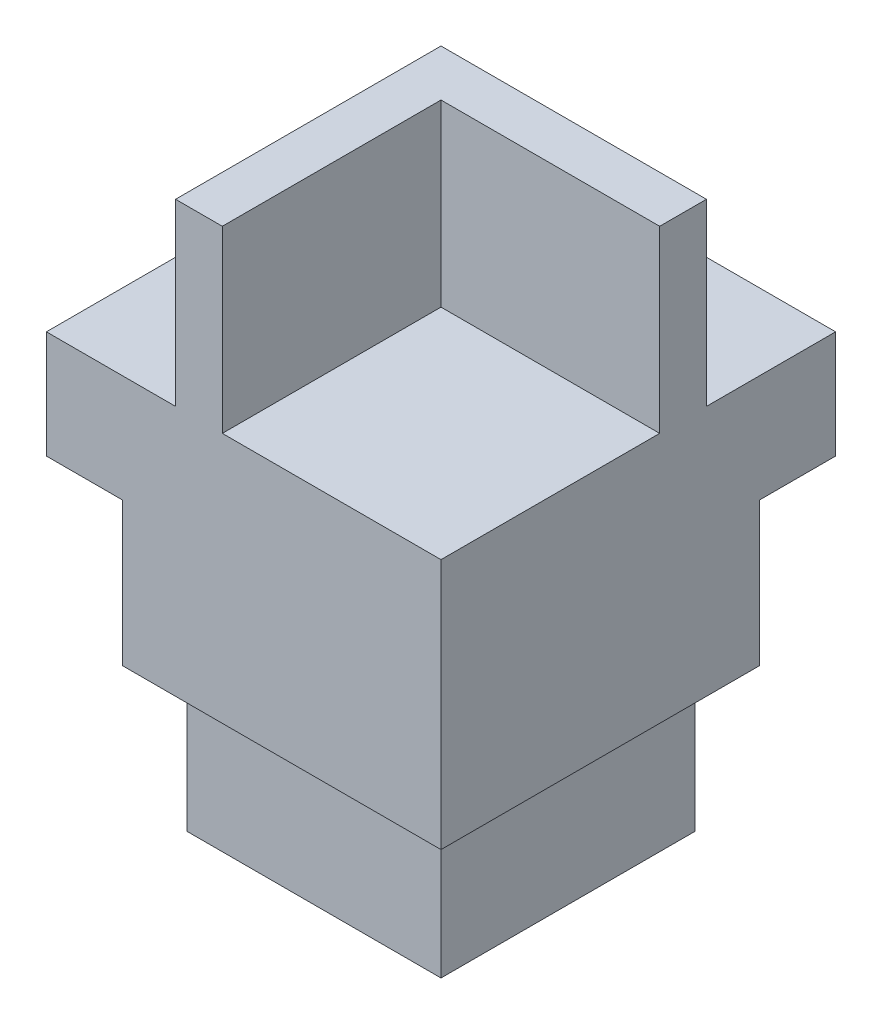
SolidWorks part; units mm, degrees
ref_plane "Front Plane" through (0, 0, 0) normal (0, 0, 1) x (1, 0, 0)
ref_plane "Top Plane" through (0, 0, 0) normal (0, 1, 0) x (1, 0, 0)
ref_plane "Right Plane" through (0, 0, 0) normal (1, 0, 0) x (0, 0, -1)
sketch "Sketch7" plane through (0, 0, 0) normal (0, 1, 0) x (1, 0, 0)
  line L1 (-15.54, -25.3407) -> (11.96, -25.3407)
  line L2 (-15.54, -25.3407) -> (-15.54, -52.8407)
  line L3 (-15.54, -52.8407) -> (11.96, -52.8407)
  line L4 (11.96, -25.3407) -> (11.96, -52.8407)
  dimension "D1" = 27.5
  dimension "D2" = 27.5
extrude "Boss-Extrude6" add sketch "Sketch7" along normal blind 40 separate body
sketch "Sketch8" plane through (0, 40, 0) normal (0, 1, 0) x (1, 0, 0)
  line L1 (11.96, -52.8407) -> (-3.28, -52.8407)
  line L2 (11.96, -52.8407) -> (11.96, -37.6007)
  line L3 (11.96, -37.6007) -> (-3.28, -37.6007)
  line L4 (-3.28, -52.8407) -> (-3.28, -37.6007)
  dimension "D1" = 15.24
  dimension "D2" = 15.24
extrude "Cut-Extrude2" cut sketch "Sketch8" against normal blind 12.5
sketch "Sketch9" plane through (0, 0, 0) normal (0, -1, 0) x (1, 0, 0)
  line L1 (11.96, 52.8407) -> (-10.24, 52.8407)
  line L2 (11.96, 52.8407) -> (11.96, 30.6407)
  line L3 (11.96, 30.6407) -> (-10.24, 30.6407)
  line L4 (-10.24, 52.8407) -> (-10.24, 30.6407)
  line L5 (11.96, 52.8407) -> (-15.54, 52.8407)
  line L6 (11.96, 52.8407) -> (11.96, 25.3407)
  line L7 (11.96, 25.3407) -> (-15.54, 25.3407)
  line L8 (-15.54, 52.8407) -> (-15.54, 25.3407)
  line M5 (-15.54, 52.8407) -> (-15.54, 25.3407)
  line M6 (-15.54, 25.3407) -> (11.96, 25.3407)
  line M7 (11.96, 25.3407) -> (11.96, 52.8407)
  line M8 (11.96, 52.8407) -> (-15.54, 52.8407)
  dimension "D1" = 22.2
  dimension "D2" = 22.2
extrude "Cut-Extrude3" cut sketch "Sketch9" against normal blind 20 contours L4 L3 M8 M5 M6 M7 region at (-10.6289, 0, 41.7407)
sketch "Sketch10" plane through (0, 0, 0) normal (0, -1, 0) x (1, 0, 0)
  line L0 (-10.24, 41.7407) -> (11.96, 41.7407) construction
  line L2 (-10.24, 52.8407) -> (-10.24, 30.6407) construction
  line L3 (11.96, 52.8407) -> (11.96, 30.6407) construction
  line L5 (-7.99, 50.5907) -> (9.71, 50.5907)
  line L6 (-7.99, 50.5907) -> (-7.99, 32.8907)
  line L7 (-7.99, 32.8907) -> (9.71, 32.8907)
  line L8 (9.71, 50.5907) -> (9.71, 32.8907)
  line L9 (-7.99, 50.5907) -> (9.71, 32.8907) construction
  line L10 (-7.99, 32.8907) -> (9.71, 50.5907) construction
  line L11 (-10.24, 52.8407) -> (11.96, 52.8407)
  line L12 (-10.24, 52.8407) -> (-10.24, 30.6407)
  line L13 (-10.24, 30.6407) -> (11.96, 30.6407)
  line L14 (11.96, 52.8407) -> (11.96, 30.6407)
  line L15 (-10.24, 52.8407) -> (11.96, 30.6407) construction
  line L16 (-10.24, 30.6407) -> (11.96, 52.8407) construction
  point P6 (0.86, 41.7407)
  point P11 (0.86, 41.7407)
  dimension "D1" = 17.7
  dimension "D2" = 17.7
extrude "Cut-Extrude4" cut sketch "Sketch10" against normal blind 10
sketch "Sketch11" plane through (0, 40, 0) normal (0, 1, 0) x (1, 0, 0)
  line L1 (11.96, -25.3407) -> (-10.5577, -25.3407)
  line L2 (11.96, -25.3407) -> (11.96, -34.3407)
  line L3 (11.96, -34.3407) -> (-6.54, -34.3407)
  line L5 (-15.54, -52.8407) -> (-6.54, -52.8407)
  line L6 (-15.54, -52.8407) -> (-15.54, -25.3407)
  line L7 (-15.54, -25.3407) -> (-4.5646, -25.3407)
  line L8 (-6.54, -52.8407) -> (-6.54, -34.3407)
  line M6 (11.96, -37.6007) -> (11.96, -25.3407)
  line M7 (11.96, -25.3407) -> (-15.54, -25.3407)
  line M8 (-15.54, -25.3407) -> (-15.54, -52.8407)
  line M9 (-15.54, -52.8407) -> (-3.28, -52.8407)
  dimension "D1" = 9
  dimension "D2" = 9
extrude "Cut-Extrude5" cut sketch "Sketch11" against normal blind 12.5 contours L8 L3 L1 M9 M6 M7 M8 region at (11.5711, 40, 29.8407)
